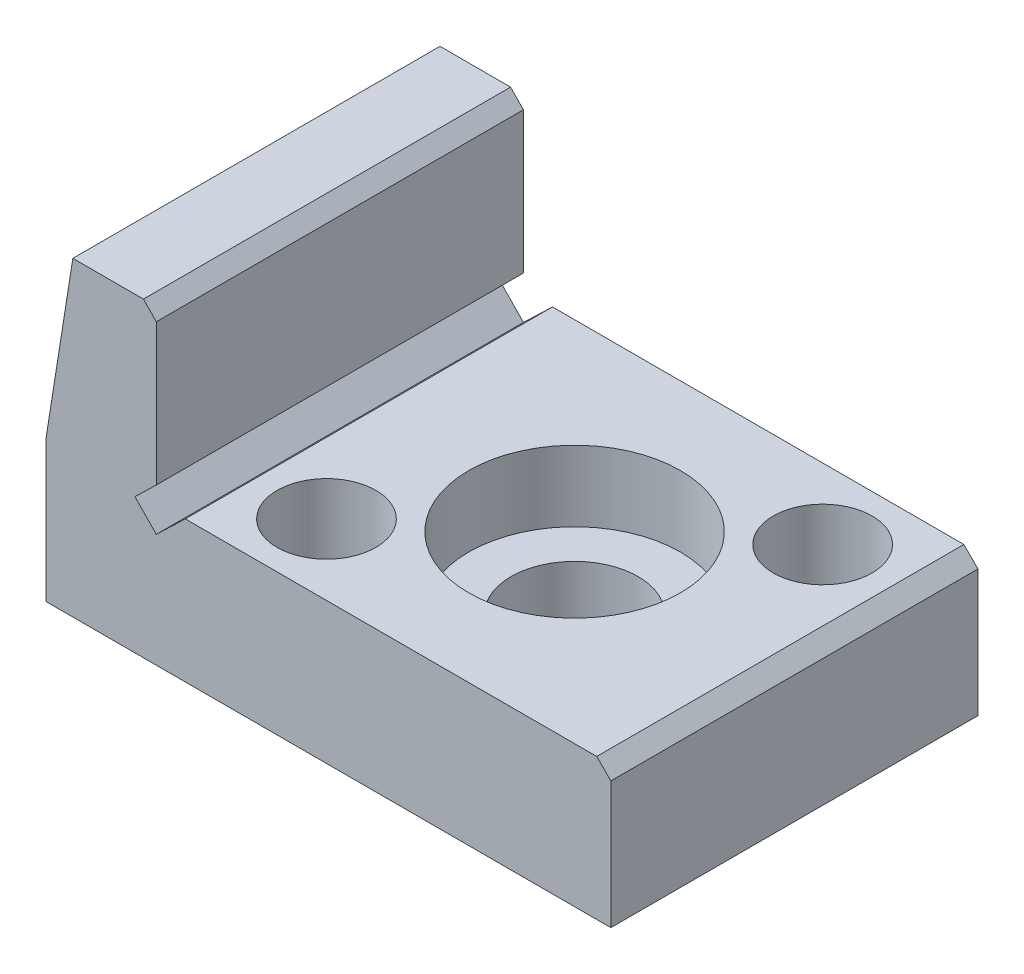
SolidWorks part; units mm, degrees
ref_plane "前视基准面" through (0, 0, 0) normal (0, 0, 1) x (1, 0, 0)
ref_plane "上视基准面" through (0, 0, 0) normal (0, 1, 0) x (1, 0, 0)
ref_plane "右视基准面" through (0, 0, 0) normal (1, 0, 0) x (0, 0, -1)
sketch "草图1" plane through (0, 0, 0) normal (0, 0, 1) x (1, 0, 0)
  line L0 (0, 0) -> (40, 0)
  line L1 (40, 0) -> (40, 9)
  line L2 (39, 10) -> (9.8629, 10)
  line L3 (6.9006, 22) -> (7.8113, 21.0638)
  line L4 (7.8113, 21.0638) -> (7.8113, 11.0524)
  line L5 (7.8113, 11.0524) -> (6.2982, 9.5805)
  line L6 (6.2982, 9.5805) -> (7.8113, 8.0251)
  line L7 (6.9006, 22) -> (1.9006, 22)
  line L8 (1.9006, 22) -> (0, 10)
  line L9 (0, 10) -> (0, 0)
  line L10 (7.8113, 8.0251) -> (9.8629, 10)
  line L11 (40, 9) -> (39, 10)
  point P3 (40, 10)
  dimension "D1" = 10
  dimension "D2" = 12
  dimension "D3" = 40
  dimension "D4" = 171
  dimension "D5" = 5
extrude "凸台-拉伸1" add sketch "草图1" along normal blind 26
sketch "草图2" plane through (0, 10, 0) normal (0, 1, 0) x (1, 0, 0)
  line L0 (39, -13) -> (9.8629, -13) construction
  line L1 (39, -26) -> (39, 0) construction
  line L2 (9.8629, -26) -> (9.8629, 0) construction
  line L3 (40, -26) -> (40, 0) construction
  line L4 (39, 0) -> (9.8629, 0) construction
  line L5 (24.4314, 0) -> (24.4314, -26) construction
  line L6 (39, -26) -> (9.8629, -26) construction
  circle A0 centre (34, -5) radius 3.5
  circle A1 centre (24.4314, -13) radius 4.5
  circle A2 centre (24.4314, -13) radius 7.5
  circle A4 centre (14.8629, -21) radius 3.5
  dimension "D1" = 9
  dimension "D2" = 15
  dimension "D3" = 7
  dimension "D4" = 6
  dimension "D5" = 5
extrude "切除-拉伸1" cut sketch "草图2" against normal blind 26 contours A4 | A1 | A0 region at (34, 10, 5) region at (24.4314, 10, 13) region at (14.8629, 10, 21)
extrude "切除-拉伸2" cut sketch "草图2<3>" against normal blind 5 contours A2 A1 region at (17.1436, 10, 13)
sketch "草图2<3>" plane through (0, 10, 0) normal (0, 1, 0) x (1, 0, 0) same geometry as "草图2"
